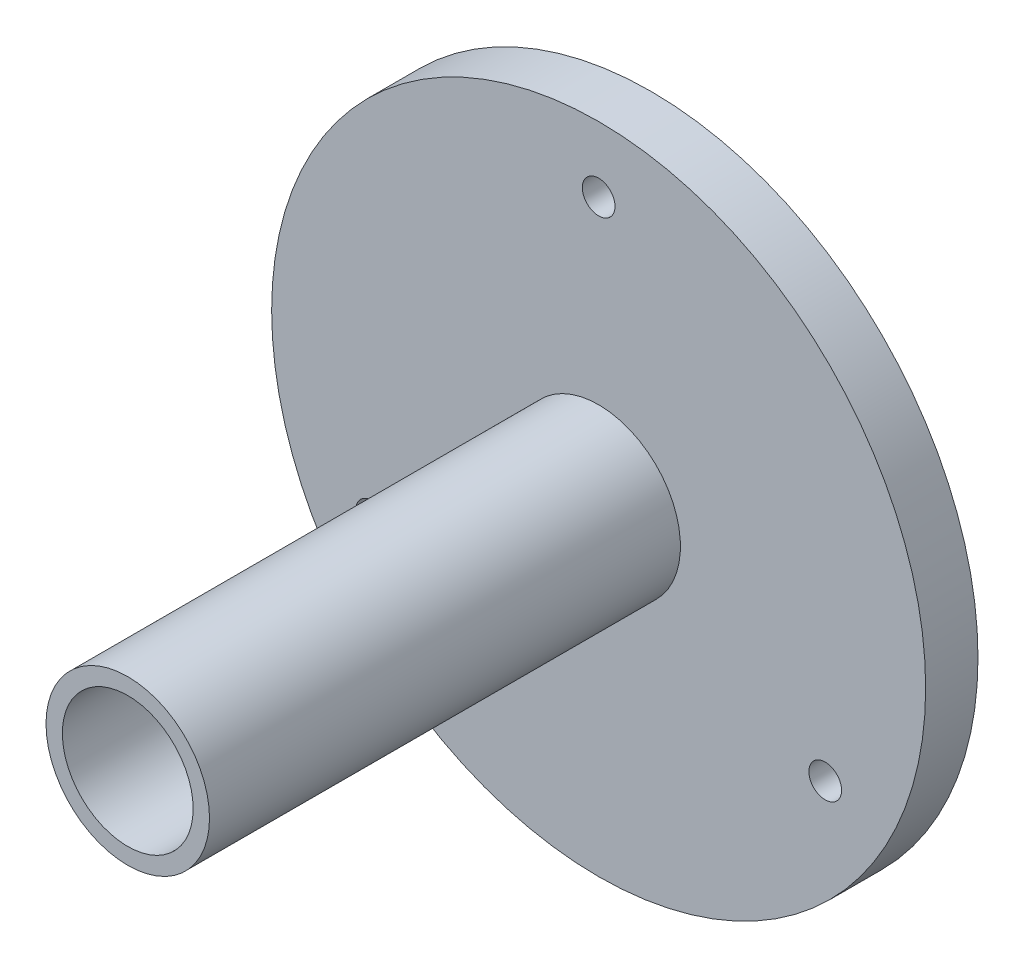
SolidWorks part; units mm, degrees
ref_plane "Front Plane" through (0, 0, 0) normal (0, 0, 1) x (1, 0, 0)
ref_plane "Top Plane" through (0, 0, 0) normal (0, 1, 0) x (1, 0, 0)
ref_plane "Right Plane" through (0, 0, 0) normal (1, 0, 0) x (0, 0, -1)
sketch "Sketch1" plane through (0, 0, 0) normal (0, 0, 1) x (1, 0, 0)
  circle A0 centre (0, 0) radius 10
  circle A1 centre (0, 0) radius 12.5
  dimension "D1" = 25
extrude "Boss-Extrude1" add sketch "Sketch1" along normal blind 80
sketch "Sketch2" plane through (0, 0, 0) normal (0, 0, -1) x (-1, 0, 0)
  circle A0 centre (0, 0) radius 50
  circle A1 centre (0, 0) radius 12.5
  dimension "D1" = 100
extrude "Boss-Extrude2" add sketch "Sketch2" against normal blind 8
sketch "Sketch3" plane through (0, 0, 8) normal (0, 0, 1) x (1, 0, 0)
  circle A0 centre (0, 40) radius 2.5
  circle A1 centre (0, 0) radius 50 construction
  dimension "D1" = 5
  dimension "D2" = 40
extrude "Cut-Extrude1" cut sketch "Sketch3" against normal blind 8
pattern_circular "CirPattern1" count 3 every 120 about axis through (0, 0, 8) along (0, 0, -1) of "Cut-Extrude1"
